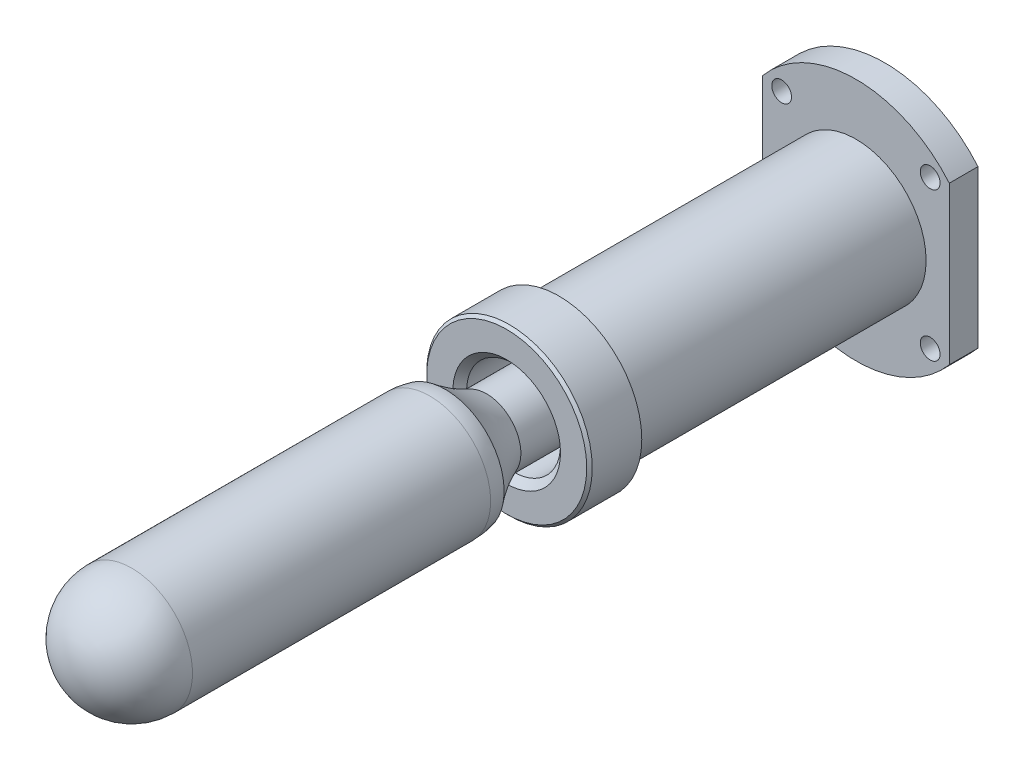
SolidWorks part; units mm, degrees
ref_plane "Front Plane" through (0, 0, 0) normal (0, 0, 1) x (1, 0, 0)
ref_plane "Top Plane" through (0, 0, 0) normal (0, 1, 0) x (1, 0, 0)
ref_plane "Right Plane" through (0, 0, 0) normal (1, 0, 0) x (0, 0, -1)
sketch "Sketch1" plane through (0, 0, 0) normal (0, 0, 1) x (-1, 0, 0)
  line L0 (-23.9, 0) -> (-7, 0)
  line L1 (-23.9, 0) -> (-40.8, 0)
  line L3 (-7, 14.2408) -> (-7, -14.2408)
  line L6 (23.9, 0) -> (40.8, 0)
  line L8 (-40.8, 14.2408) -> (-40.8, -14.2408)
  line L11 (23.9, 0) -> (7, 0)
  line L12 (-23.9, 0) -> (-10.465, 13.435)
  line L14 (7, 14.2408) -> (7, -14.2408)
  line L18 (40.8, 14.2408) -> (40.8, -14.2408)
  line L21 (-23.9, 0) -> (-37.3704, 13.4704)
  line L22 (0, 0) -> (0, 22.2053) construction
  line L23 (0, 0) -> (0, 35) construction
  line L24 (23.9, 0) -> (37.3704, 13.4704) construction
  line L25 (23.9, 0) -> (28.0712, 10.0703) construction
  line L26 (23.9, 0) -> (33.9703, 4.1712) construction
  arc A0 (-40.8, -14.2408) -> (-7, -14.2408) centre (-23.9, 0) ccw
  circle A1 centre (28.0712, 10.0703) radius 1.5
  arc A2 (7, -14.2408) -> (40.8, -14.2408) centre (23.9, 0) ccw
  arc A4 (-7, 14.2408) -> (-40.8, 14.2408) centre (-23.9, 0) ccw
  circle A5 centre (0, 0) radius 4.9
  circle A6 centre (0, 35) radius 2
  arc A7 (40.8, 14.2408) -> (7, 14.2408) centre (23.9, 0) ccw
  circle A8 centre (-37.3704, 13.4704) radius 1.79
  circle A9 centre (-10.465, 13.435) radius 1.79
  circle A10 centre (-10.465, -13.435) radius 1.79
  circle A11 centre (-37.3704, -13.4704) radius 1.79
  circle A12 centre (10.465, 13.435) radius 1.79
  circle A13 centre (10.465, -13.435) radius 1.79
  circle A14 centre (37.3704, -13.4704) radius 1.79
  circle A15 centre (37.3704, 13.4704) radius 1.79
  circle A16 centre (-23.9, 0) radius 12.7
  circle A17 centre (23.9, 0) radius 12.7
  circle A18 centre (19.7288, 10.0703) radius 1.5
  circle A19 centre (13.8297, 4.1712) radius 1.5
  circle A20 centre (13.8297, -4.1712) radius 1.5
  circle A21 centre (19.7288, -10.0703) radius 1.5
  circle A22 centre (28.0712, -10.0703) radius 1.5
  circle A23 centre (33.9703, -4.1712) radius 1.5
  circle A24 centre (33.9703, 4.1712) radius 1.5
  circle A25 centre (23.9, 0) radius 5.15
  circle A26 centre (23.9, 0) radius 8.7
  dimension "D1" = 44.2
  dimension "D2" = 44.2
  dimension "D3" = 16.9
  dimension "D7" = 9.8
  dimension "D12" = 3.58
  dimension "D13" = 3.58
  dimension "D14" = 25.4
  dimension "D16" = 4
  dimension "D19" = 3
  dimension "D21" = 10.3
  dimension "D4" = 16.9
  dimension "D5" = 16.9
  dimension "D6" = 16.9
  dimension "D8" = 19
  dimension "D9" = 90
  dimension "D10" = 19.05
  dimension "D11" = 45
  dimension "D15" = 35
  dimension "D17" = 22.5
  dimension "D18" = 10.9
  dimension "D20" = 8
  dimension "D22" = 4
extrude "Boss-Extrude1" add sketch "Sketch1" along normal blind 5.2 contours L11 A17 L6 L18 A7 L14 A15 A12 | L6 A17 L11 L14 A2 L18 A14 A13 | A20 | A21 | L6 A26 L11 A17 A23 A22 A21 A20 | A22 | A23 | A24 | A1 | A18 | A19 | L11 A26 L6 A17 A24 A19 A18 A1 | A26 L11 A25 L6 | A26 L6 A25 L11 region at (-23.9, -5.3445, 0) region at (-30.825, 0.1945, 0) region at (-23.9, -8.984, 0) region at (-34.6, 0.284, 0) region at (-23.8991, -12.7649, 0) region at (-23.8991, 12.7649, 0) region at (-28.0712, -10.0703, 0) region at (-19.7288, -10.0703, 0) region at (-13.8297, -4.1712, 0) region at (-13.8297, 4.1712, 0) region at (-19.7288, 10.0703, 0) region at (-28.0712, 10.0703, 0) region at (-33.9703, 4.1712, 0) region at (-33.9703, -4.1712, 0)
extrude "Boss-Extrude2" add sketch "Sketch1<12>" along normal blind 59 contours L1 A16 L0 | L0 A16 L12 | L12 A16 L21 | L21 A16 L1 | A17 L11 L6 | A17 L6 L11 | A21 | A20 | A19 | A22 | A24 | A1 | A18 | A23 region at (16.2773, -3.1574, 0) region at (23.9, 5.39, 0) region at (23.9, -7.6227, 0) region at (31.5227, -3.1574, 0) region at (-23.9, -8.984, 0) region at (-34.6, 0.284, 0)
sketch "Sketch1<12>" plane through (0, 0, 0) normal (0, 0, 1) x (-1, 0, 0) same geometry as "Sketch1"
sketch "Sketch3" plane through (0, 0, 0) normal (0, 1, 0) x (1, 0, 0)
  line L9 (-36.1357, -65.0531) -> (-23.9, -65.0531) construction
  line L10 (-28.1225, -59.0762) -> (-23.9, -59.0762)
  line L15 (-30.1225, -72.1224) -> (-30.1225, -61.0762)
  line L16 (-34.9, -136.3775) -> (-34.9, -82.3775)
  line L17 (-23.9, -59.0762) -> (-23.9, -147.3775)
  arc A4 (-30.1225, -61.0762) -> (-28.1225, -59.0762) centre (-28.1225, -61.0762) cw
  arc A5 (-34.9, -82.3775) -> (-34.5373, -79.5762) centre (-23.9, -82.3775) cw
  arc A6 (-23.9, -147.3775) -> (-34.9, -136.3775) centre (-23.9, -136.3775) cw
  spline S1 degree 2 poles (-34.5373, -79.5762) (-31.796, -76.1482) (-30.1225, -72.1224) knots 0 0 0 1 1 1
  point P7 (-27.0112, 68.47)
  point P19 (-23.9, 98.2713)
revolve "Revolve1" add sketch "Sketch3" angle 360 about L17
sketch "Sketch4" plane through (0, 0, 59) normal (0, 0, 1) x (1, 0, 0)
  circle A0 centre (-23.9, 0) radius 15
  circle A1 centre (-23.9, 0) radius 8.5
  dimension "D1" = 30
  dimension "D2" = 6.5
extrude "Boss-Extrude3" add sketch "Sketch4" along normal blind 9.47
delete or keep bodies "Body-Delete/Keep 1" type delete bodies bodies 103
chamfer "Chamfer1" distance 0.5 angle 45 1 edges at (-8.9, 0, 68.47)
extrude "Cut-Extrude1" cut sketch "Sketch1<14>" along normal blind 40 contours A19 | A20 | A21 | A22 | A23 | A24 | A1 | A18 region at (-28.0712, -10.0703, 0) region at (-19.7288, -10.0703, 0) region at (-13.8297, -4.1712, 0) region at (-13.8297, 4.1712, 0) region at (-19.7288, 10.0703, 0) region at (-28.0712, 10.0703, 0) region at (-33.9703, 4.1712, 0) region at (-33.9703, -4.1712, 0)
sketch "Sketch1<14>" plane through (0, 0, 0) normal (0, 0, 1) x (-1, 0, 0) same geometry as "Sketch1"
chamfer "Chamfer2" distance 1.25 angle 45 1 edges at (-15.4, 0, 68.47)
